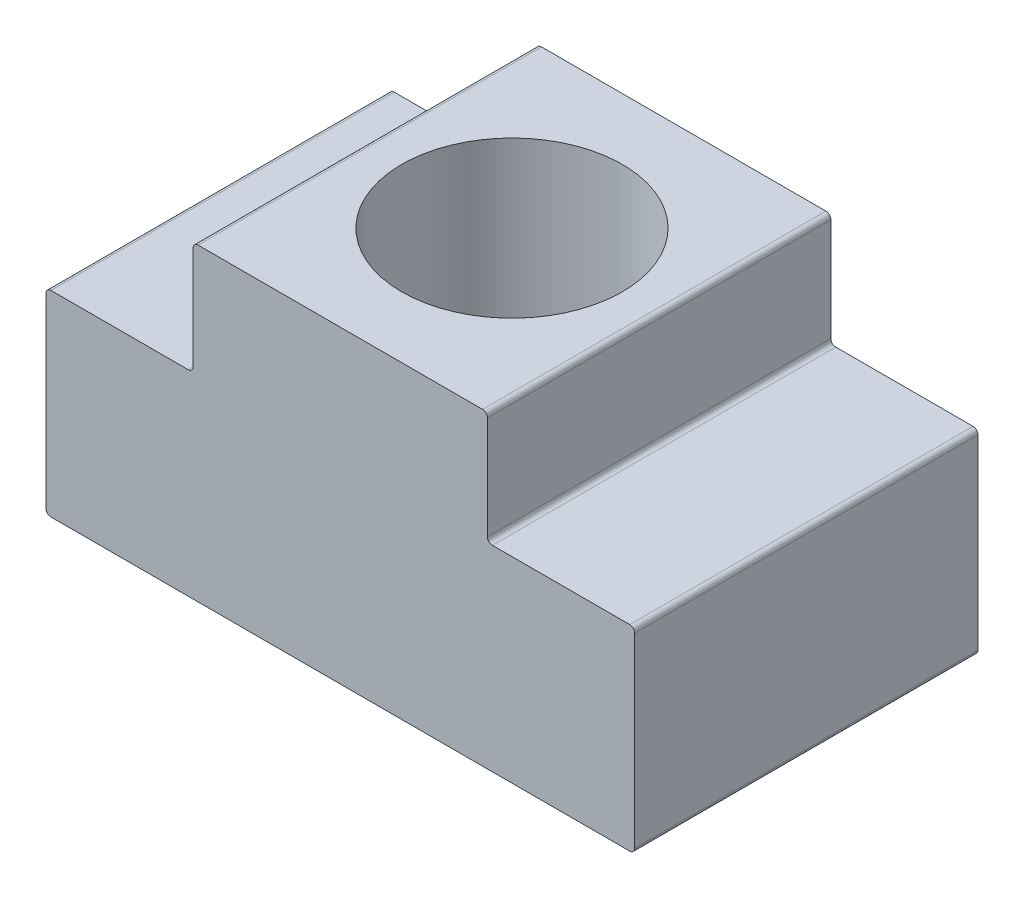
SolidWorks part; units mm, degrees
material "Chrome Stainless Steel"
ref_plane "Front Plane" through (0, 0, 0) normal (0, 0, 1) x (1, 0, 0)
ref_plane "Top Plane" through (0, 0, 0) normal (0, 1, 0) x (1, 0, 0)
ref_plane "Right Plane" through (0, 0, 0) normal (1, 0, 0) x (0, 0, -1)
sketch "Sketch1" plane through (0, 0, 0) normal (0, 0, 1) x (1, 0, 0)
  line L0 (0, 6.3) -> (3, 6.3)
  line L1 (0, -3.575) -> (0, 3.575) construction
  line L2 (3, 6.3) -> (3, 4)
  line L3 (3, 4) -> (6, 4)
  line L4 (6, 4) -> (6, 0)
  line L5 (3.85, 0) -> (-3.85, 0) construction
  line L6 (6, 0) -> (0, 0)
  line L7 (0, 0) -> (0, 6.3)
  dimension "D1" = 3
  dimension "D2" = 2.3
  dimension "D3" = 4
  dimension "D4" = 6
extrude "Boss-Extrude1" add sketch "Sketch1" along normal blind 7
mirror "Mirror1" about plane through (0, 0, 0) normal (1, 0, 0) of "Boss-Extrude1"
sketch "Sketch2" plane through (0, 6.3, 0) normal (0, 1, 0) x (1, 0, 0)
  line L0 (0, -3.575) -> (0, 3.575) construction
  line L1 (-3.575, 0) -> (3.575, 0) construction
  circle A0 centre (0, -3.5) radius 2.25
  dimension "D1" = 4.5
  dimension "D2" = 3.5
extrude "Cut-Extrude1" cut sketch "Sketch2" against normal blind 7
fillet "Fillet1" radius 0.1 8 edges at (3, 4, 3.5) (6, 0, 3.5) (6, 4, 3.5) (-3, 6.3, 3.5) (3, 6.3, 3.5) (-6, 0, 3.5) (-6, 4, 3.5) (-3, 4, 3.5)
